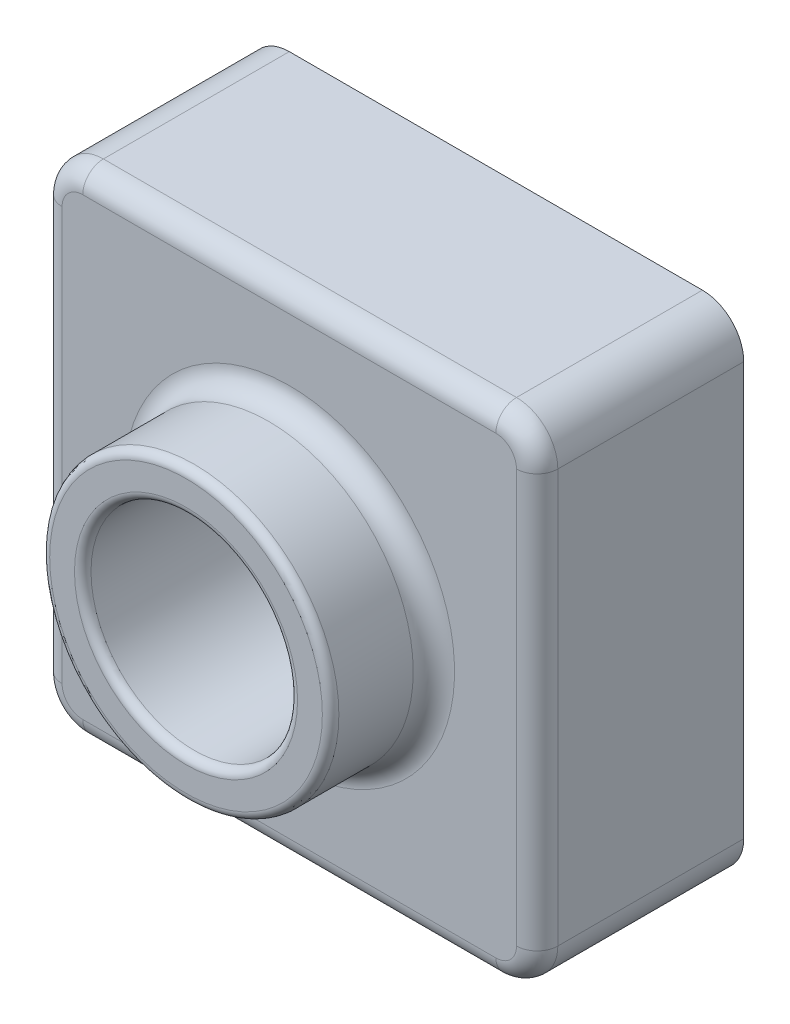
SolidWorks part; units mm, degrees
ref_plane "Front" through (0, 0, 0) normal (0, 0, 1) x (1, 0, 0)
ref_plane "Top" through (0, 0, 0) normal (0, 1, 0) x (1, 0, 0)
ref_plane "Right" through (0, 0, 0) normal (1, 0, 0) x (0, 0, -1)
other "Configuration Table"
sketch "Sketch1" plane through (0, 0, 0) normal (0, 0, 1) x (1, 0, 0)
  line L1 (0, 0) -> (120, 0)
  line L2 (0, 0) -> (0, 120)
  line L3 (0, 120) -> (120, 120)
  line L4 (120, 0) -> (120, 120)
  dimension "D1" = 120
  dimension "D2" = 120
extrude "Extrude1" add sketch "Sketch1" along normal blind 50
sketch "Sketch2" plane through (0, 0, 50) normal (0, 0, 1) x (1, 0, 0)
  line L0 (120, 120) -> (0, 120) construction
  line L1 (120, 0) -> (120, 120) construction
  circle A0 centre (60, 60) radius 35
  dimension "D3" = 70
  dimension "D1" = 60
  dimension "D2" = 60
extrude "Extrude2" add sketch "Sketch2" along normal blind 25
sketch "Sketch3" plane through (0, 0, 75) normal (0, 0, 1) x (1, 0, 0)
  circle A0 centre (60, 60) radius 25
  circle A1 centre (60, 60) radius 35 construction
  dimension "D1" = 50
extrude "Cut-Extrude1" cut sketch "Sketch3" against normal through all
fillet "Fillet1" radius 10 4 edges at (0, 120, 25) (120, 120, 25) (120, 0, 25) (0, 0, 25)
fillet "Fillet2" radius 5 9 edges at (25, 60, 50) (0, 60, 50) (60, 120, 50) (60, 0, 50) (120, 60, 50) (2.9289, 2.9289, 50) (117.0711, 2.9289, 50) (117.0711, 117.0711, 50) (2.9289, 117.0711, 50)
fillet "Fillet3" radius 2 2 edges at (95, 60, 75) (85, 60, 75)
shell "Shell1" thickness 2
